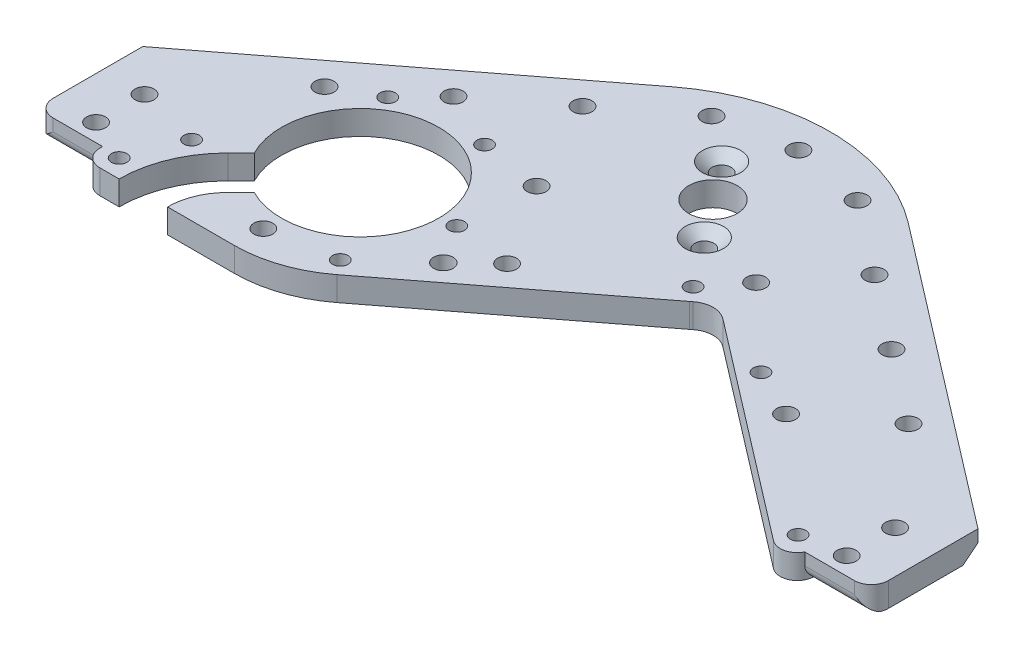
SolidWorks part; units mm, degrees
material "Alum Plate"
ref_plane "Front Plane" through (0, 0, 0) normal (0, 0, 1) x (1, 0, 0)
ref_plane "Top Plane" through (0, 0, 0) normal (0, 1, 0) x (1, 0, 0)
ref_plane "Right Plane" through (0, 0, 0) normal (1, 0, 0) x (0, 0, -1)
sketch "Top Layout" plane through (0, 0, 0) normal (0, 1, 0) x (1, 0, 0)
  line L0 (-114.046, -123.825) -> (-104.775, -123.825) construction
  line L1 (-104.775, -142.875) -> (-101.6, -142.875)
  line L2 (-104.775, -142.875) -> (-104.775, -104.775)
  line L3 (-104.775, -104.775) -> (-101.6, -104.775)
  line L4 (-101.6, -142.875) -> (-101.6, -104.775)
  line L5 (-104.775, -142.875) -> (-101.6, -104.775) construction
  line L6 (-104.775, -104.775) -> (-101.6, -142.875) construction
  line L7 (-19.05, -105.8164) -> (-101.6, -105.8164)
  line L8 (-19.05, -105.8164) -> (-19.05, -141.8336)
  line L9 (-19.05, -141.8336) -> (-101.6, -141.8336)
  line L10 (-101.6, -105.8164) -> (-101.6, -141.8336)
  line L11 (-19.05, -105.8164) -> (-101.6, -141.8336) construction
  line L12 (-19.05, -141.8336) -> (-101.6, -105.8164) construction
  line L13 (-133.096, -85.725) -> (-114.046, -85.725)
  line L14 (-133.096, -85.725) -> (-133.096, -161.925)
  line L15 (-133.096, -161.925) -> (-114.046, -161.925)
  line L16 (-114.046, -85.725) -> (-114.046, -161.925)
  line L17 (-133.096, -85.725) -> (-114.046, -161.925) construction
  line L18 (-133.096, -161.925) -> (-114.046, -85.725) construction
  line L19 (-104.775, -123.825) -> (0, -123.825) construction
  line L20 (0, -123.825) -> (0, 0) construction
  line L21 (-52.3528, -40.1717) -> (0, 0) construction
  line L22 (-70.6449, -16.3328) -> (-18.2922, 23.8388)
  line L23 (-34.0606, -64.0105) -> (18.2922, -23.8388)
  line L24 (-30.9251, 40.3023) -> (-122.2248, -29.7544)
  line L25 (-153.9748, -53.975) -> (-153.9748, -123.825)
  line L26 (-109.5248, -162.052) -> (109.5248, -162.052)
  line L27 (0, -162.052) -> (0, -123.825) construction
  line L28 (-109.5248, -162.052) -> (-109.5248, -20.0093) construction
  line L29 (-104.775, -142.875) -> (-104.775, -152.527)
  line L30 (-104.775, -152.527) -> (104.775, -152.527)
  line L31 (104.775, -104.775) -> (101.6, -104.775)
  line L32 (-144.4498, -73.025) -> (-109.5248, -73.025)
  line L33 (-144.4498, -73.025) -> (-144.4498, -123.825)
  line L34 (-144.4498, -123.825) -> (-109.5248, -123.825) construction
  line L35 (-109.5248, -73.025) -> (-109.5248, -162.052)
  line L36 (-144.4498, -73.025) -> (-109.5248, -123.825) construction
  line L37 (-144.4498, -123.825) -> (-109.5248, -73.025) construction
  line L38 (101.6, -142.875) -> (101.6, -104.775)
  line L39 (104.775, -142.875) -> (101.6, -142.875)
  line L40 (104.775, -142.875) -> (104.775, -104.775)
  line L41 (104.775, -142.875) -> (104.775, -152.527)
  line L42 (109.5248, -162.052) -> (109.5248, -20.0093) construction
  line L43 (30.9251, 40.3023) -> (122.2248, -29.7544)
  line L45 (19.05, -141.8336) -> (101.6, -141.8336)
  line L46 (101.6, -105.8164) -> (101.6, -141.8336)
  line L47 (19.05, -105.8164) -> (101.6, -105.8164)
  line L48 (19.05, -105.8164) -> (19.05, -141.8336)
  line L49 (133.096, -161.925) -> (114.046, -161.925)
  line L50 (114.046, -85.725) -> (114.046, -161.925)
  line L51 (133.096, -85.725) -> (114.046, -85.725)
  line L52 (133.096, -85.725) -> (133.096, -161.925)
  line L53 (144.4498, -123.825) -> (109.5248, -123.825) construction
  line L54 (109.5248, -73.025) -> (109.5248, -162.052)
  line L55 (144.4498, -73.025) -> (109.5248, -73.025)
  line L56 (144.4498, -73.025) -> (144.4498, -123.825)
  line L57 (-109.5248, -123.825) -> (-109.5248, -162.052) construction
  line L62 (-153.9748, -53.975) -> (-122.2248, -53.975)
  line L63 (-122.2248, -53.975) -> (-122.2248, -29.7544)
  line L64 (-144.4498, -123.825) -> (-153.9748, -123.825)
  line L65 (153.9748, -53.975) -> (153.9748, -123.825)
  line L66 (109.5248, -123.825) -> (109.5248, -162.052) construction
  line L67 (144.4498, -123.825) -> (153.9748, -123.825)
  line L68 (122.2248, -29.7544) -> (122.2248, -53.975)
  line L73 (-104.775, -104.775) -> (-104.775, -16.3647) construction
  line L74 (-95.25, -162.052) -> (-95.25, -9.0559) construction
  line L75 (-109.5248, -162.052) -> (-109.5248, -123.825) construction
  line L76 (109.5248, -162.052) -> (109.5248, -123.825) construction
  line L77 (122.2248, -53.975) -> (153.9748, -53.975)
  line L83 (104.775, -155.5496) -> (-104.775, -155.5496) construction
  line L88 (95.25, -162.052) -> (95.25, -9.0559) construction
  line L89 (104.775, -104.775) -> (104.775, -16.3647) construction
  line L92 (-104.775, -152.527) -> (-104.775, -162.052) construction
  line L93 (-14.605, -76.327) -> (14.605, -76.327)
  line L94 (-14.605, -76.327) -> (-14.605, -152.527)
  line L95 (-14.605, -152.527) -> (14.605, -152.527)
  line L96 (14.605, -76.327) -> (14.605, -152.527)
  line L97 (-14.605, -76.327) -> (14.605, -152.527) construction
  line L98 (-14.605, -152.527) -> (14.605, -76.327) construction
  line L99 (104.775, -152.527) -> (104.775, -162.052) construction
  line L100 (-19.05, -105.8164) -> (0, -105.8164) construction
  line L107 (0, -105.8164) -> (19.05, -105.8164) construction
  line L108 (104.775, -123.825) -> (114.046, -123.825) construction
  circle A0 centre (0, 0) radius 114.3
  circle A1 centre (0, 0) radius 6.35
  circle A2 centre (-52.3528, -40.1717) radius 17.8
  circle A3 centre (0, 0) radius 30.0482
  circle A4 centre (-52.3528, -40.1717) radius 30.0482
  arc A5 (-30.9251, 40.3023) -> (30.9251, 40.3023) centre (0, 0) cw
  point P2 (-103.1875, -123.825)
  point P7 (-60.325, -123.825)
  point P12 (-123.571, -123.825)
  point P30 (-126.9873, -98.425)
  point P35 (0, -114.427)
  point P53 (0, -152.527)
  dimension "D1" = 35.6
  dimension "D2" = 12.7
  dimension "D3" = 228.6
  dimension "D11" = 60.0964
  dimension "D12" = 50.8
  dimension "D14" = 52.5
  dimension "D4" = 3.175
  dimension "D5" = 19.05
  dimension "D6" = 76.2
  dimension "D7" = 82.55
  dimension "D8" = 38.1
  dimension "D9" = 104.775
  dimension "D10" = 18.0086
  dimension "D13" = 9.525
  dimension "D15" = 4.7498
  dimension "D16" = 9.525
  dimension "D17" = 9.652
  dimension "D18" = 50.8
  dimension "D19" = 12.446
  dimension "D20" = 65.9892
  dimension "D21" = 19.05
  dimension "D22" = 34.925
  dimension "D23" = 123.825
  dimension "D24" = 12.7
  dimension "D25" = 9.525
  dimension "D26" = 29.21
  dimension "D27" = 76.2
  dimension "D28" = 3.0226
sketch "Side Layout" plane through (0, 0, 0) normal (1, 0, 0) x (0, 0, -1)
  line L0 (0, -38.1) -> (0, 33.7344) construction
  line L1 (-114.3, -20.955) -> (114.3, -20.955)
  line L2 (-114.3, -20.955) -> (-114.3, -33.655)
  line L3 (-114.3, -33.655) -> (114.3, -33.655)
  line L4 (114.3, -20.955) -> (114.3, -33.655)
  line L5 (-114.3, -20.955) -> (114.3, -33.655) construction
  line L6 (-114.3, -33.655) -> (114.3, -20.955) construction
  line L7 (-9.525, -32.9406) -> (9.525, -32.9406)
  line L8 (-9.525, -32.9406) -> (-9.525, -38.1)
  line L9 (-9.525, -38.1) -> (9.525, -38.1)
  line L10 (9.525, -32.9406) -> (9.525, -38.1)
  line L11 (-9.525, -32.9406) -> (9.525, -38.1) construction
  line L12 (-9.525, -38.1) -> (9.525, -32.9406) construction
  line L13 (-11.9126, -29.3338) -> (11.9126, -29.3338)
  line L14 (-11.9126, -29.3338) -> (-11.9126, -32.9406)
  line L15 (-11.9126, -32.9406) -> (11.9126, -32.9406)
  line L16 (11.9126, -29.3338) -> (11.9126, -32.9406)
  line L17 (-11.9126, -29.3338) -> (11.9126, -32.9406) construction
  line L18 (-11.9126, -32.9406) -> (11.9126, -29.3338) construction
  line L19 (-6.35, -32.9406) -> (6.35, -32.9406)
  line L20 (-6.35, -32.9406) -> (-6.35, 33.7344)
  line L21 (-6.35, 33.7344) -> (6.35, 33.7344)
  line L22 (6.35, -32.9406) -> (6.35, 33.7344)
  line L23 (-6.35, -32.9406) -> (6.35, 33.7344) construction
  line L24 (-6.35, 33.7344) -> (6.35, -32.9406) construction
  line L25 (-162.052, 0) -> (-123.825, 0) construction
  line L26 (114.3, -33.655) -> (114.3, 0) construction
  line L27 (-142.875, 19.05) -> (-104.775, 19.05)
  line L28 (-40.1717, -9.525) -> (-40.1717, 5.4) construction
  line L29 (-142.875, 19.05) -> (-142.875, -19.05)
  line L30 (-142.875, -19.05) -> (-104.775, -19.05)
  line L31 (-104.775, 19.05) -> (-104.775, -19.05)
  line L32 (-142.875, 19.05) -> (-104.775, -19.05) construction
  line L33 (-142.875, -19.05) -> (-104.775, 19.05) construction
  line L34 (-130.175, -38.1) -> (-117.9516, -38.1) construction
  line L35 (-57.9717, -14.6) -> (-22.3717, -14.6)
  line L36 (-30.0482, -2.794) -> (30.0482, -2.794)
  line L37 (-30.0482, -2.794) -> (-30.0482, -20.955)
  line L38 (-30.0482, -20.955) -> (30.0482, -20.955)
  line L39 (30.0482, -2.794) -> (30.0482, -20.955)
  line L40 (-30.0482, -2.794) -> (30.0482, -20.955) construction
  line L41 (-30.0482, -20.955) -> (30.0482, -2.794) construction
  line L42 (-30.0482, -2.794) -> (-30.0482, 0) construction
  line L43 (-123.825, 0) -> (0, 0) construction
  line L44 (-57.9717, -14.6) -> (-57.9717, 25.4)
  line L45 (-57.9717, 25.4) -> (-22.3717, 25.4)
  line L46 (-22.3717, -14.6) -> (-22.3717, 25.4)
  line L47 (-19.05, 0) -> (19.05, 0)
  line L48 (-19.05, 0) -> (-19.05, -1.9812)
  line L49 (-19.05, -1.9812) -> (19.05, -1.9812)
  line L50 (19.05, 0) -> (19.05, -1.9812)
  line L51 (-19.05, 0) -> (19.05, -1.9812) construction
  line L52 (-19.05, -1.9812) -> (19.05, 0) construction
  line L53 (-70.2199, -3.175) -> (-10.1235, -3.175)
  line L54 (-70.2199, -3.175) -> (-70.2199, -15.875)
  line L55 (-70.2199, -15.875) -> (-10.1235, -15.875)
  line L56 (-10.1235, -3.175) -> (-10.1235, -15.875)
  line L57 (-70.2199, -3.175) -> (-10.1235, -15.875) construction
  line L58 (-70.2199, -15.875) -> (-10.1235, -3.175) construction
  line L59 (-40.1717, -9.525) -> (-40.1717, 0) construction
  line L60 (-57.9717, -14.6) -> (-22.3717, 25.4) construction
  line L61 (-57.9717, 25.4) -> (-22.3717, -14.6) construction
  line L62 (-22.3717, 0) -> (-57.9717, 0) construction
  line L63 (-137.8162, 0) -> (-123.825, -13.9912) construction
  line L64 (-139.065, 15.24) -> (-108.585, 15.24) construction
  line L65 (-139.065, 15.24) -> (-139.065, -15.24) construction
  line L66 (-139.065, -15.24) -> (-108.585, -15.24) construction
  line L67 (-108.585, 15.24) -> (-108.585, -15.24) construction
  line L68 (-139.065, 15.24) -> (-108.585, -15.24) construction
  line L69 (-139.065, -15.24) -> (-108.585, 15.24) construction
  line L70 (-137.8162, 0) -> (-123.825, 13.9912) construction
  line L71 (-123.825, -13.9912) -> (-109.8338, 0) construction
  line L72 (-123.825, 13.9912) -> (-109.8338, 0) construction
  line L73 (-137.8162, 0) -> (-109.8338, 0) construction
  line L74 (-123.825, -13.9912) -> (-123.825, 13.9912) construction
  line L75 (-6.35, 17.8594) -> (6.35, 17.8594)
  line L76 (114.3, 0) -> (-114.3, 0) construction
  line L77 (-22.3717, 19.05) -> (-6.35, 19.05) construction
  line L78 (-123.825, 38.1) -> (-97.9206, 38.1) construction
  line L79 (-19.05, -3.5814) -> (19.05, -3.5814)
  line L80 (-19.05, -3.5814) -> (-19.05, -1.9812)
  line L81 (-19.05, -1.9812) -> (19.05, -1.9812)
  line L82 (19.05, -3.5814) -> (19.05, -1.9812)
  line L83 (-19.05, -3.5814) -> (19.05, -1.9812) construction
  line L84 (-19.05, -1.9812) -> (19.05, -3.5814) construction
  line L85 (-8.7376, -16.7608) -> (8.7376, -16.7608)
  line L86 (-8.7376, -16.7608) -> (-8.7376, -29.3338)
  line L87 (-8.7376, -29.3338) -> (8.7376, -29.3338)
  line L88 (8.7376, -16.7608) -> (8.7376, -29.3338)
  line L89 (-8.7376, -16.7608) -> (8.7376, -29.3338) construction
  line L90 (-8.7376, -29.3338) -> (8.7376, -16.7608) construction
  line L91 (-8.7376, -3.5814) -> (8.7376, -3.5814)
  line L92 (-8.7376, -3.5814) -> (-8.7376, -16.1544)
  line L93 (-8.7376, -16.1544) -> (8.7376, -16.1544)
  line L94 (8.7376, -3.5814) -> (8.7376, -16.1544)
  line L95 (-8.7376, -3.5814) -> (8.7376, -16.1544) construction
  line L96 (-8.7376, -16.1544) -> (8.7376, -3.5814) construction
  circle A0 centre (-123.825, 0) radius 18.0086
  circle A1 centre (-123.825, 0) radius 38.1
  circle A2 centre (-139.065, 15.24) radius 1.905
  circle A3 centre (-108.585, 15.24) radius 1.905
  circle A4 centre (-108.585, -15.24) radius 1.905
  circle A5 centre (-139.065, -15.24) radius 1.905
  circle A6 centre (-137.8162, 0) radius 1.6002
  circle A7 centre (-123.825, 13.9912) radius 1.6002
  circle A8 centre (-109.8338, 0) radius 1.6002
  circle A9 centre (-123.825, -13.9912) radius 1.6002
  point P0 (0, -27.305)
  point P6 (0, -31.1372)
  point P7 (0, -35.5203)
  point P21 (0, 0.3969)
  point P32 (0, -11.8745)
  point P43 (0, -0.9906)
  point P55 (-40.1717, -9.525)
  point P72 (-40.1717, 5.4)
  point P88 (0, -23.0473)
  point P93 (0, -2.7813)
  point P102 (0, -9.8679)
  dimension "D17" = 3.81
  dimension "D18" = 3.2004
  dimension "D1" = 12.7
  dimension "D2" = 5.1594
  dimension "D3" = 19.05
  dimension "D4" = 3.6068
  dimension "D5" = 23.8252
  dimension "D6" = 12.7
  dimension "D7" = 18.161
  dimension "D8" = 1.9812
  dimension "D9" = 12.7
  dimension "D10" = 40
  dimension "D11" = 25.4
  dimension "D12" = 50.8
  dimension "D13" = 41.275
  dimension "D14" = 30.48
  dimension "D15" = 4.445
  dimension "D16" = 19.7866
  dimension "D19" = 15.875
  dimension "D20" = 6.35
  dimension "D21" = 38.1
  dimension "D22" = 1.6002
  dimension "D23" = 38.1
  dimension "D24" = 17.4752
  dimension "D25" = 12.573
ref_plane "Plane1" through (0, 25.4, 0) normal (0, 1, 0) x (1, 0, 0)
sketch "Sketch3" plane through (0, 25.4, 0) normal (0, 1, 0) x (1, 0, 0)
  line L0 (-104.775, -36.3747) -> (-30.9251, 20.2924)
  line L1 (-104.775, -104.775) -> (-104.775, -16.3647) construction
  line L2 (0, -200130.175) -> (0, 199882.0484) construction
  line L3 (-30.9251, 40.3023) -> (-122.2248, -29.7544) construction
  line L5 (-104.775, -36.3747) -> (-104.775, -77.6497)
  line L6 (-92.075, -77.6497) -> (-104.775, -77.6497)
  line L7 (30.9251, 20.2924) -> (104.775, -36.3747)
  line L8 (104.775, -77.6497) -> (92.075, -77.6497)
  line L9 (104.775, -36.3747) -> (104.775, -77.6497)
  line L11 (104.775, -104.775) -> (104.775, -16.3647) construction
  line L12 (30.9251, 40.3023) -> (122.2248, -29.7544) construction
  line L13 (92.075, -74.6536) -> (24.1423, -22.5271)
  line L14 (-32.2514, -66.3682) -> (20.1013, -26.1965)
  line L15 (-30.9251, 20.2924) -> (0, 44.022)
  line L16 (0, 44.022) -> (30.9251, 20.2924)
  line L17 (-92.075, -77.6497) -> (-92.075, -73.1917)
  line L19 (-92.075, -73.1917) -> (-52.3528, -73.1917)
  line L20 (92.075, -74.6536) -> (92.075, -77.6497)
  circle A1 centre (-52.3528, -40.1717) radius 20.6375
  circle A2 centre (0, 0) radius 6.35
  circle A3 centre (0, 0) radius 6.35 construction
  arc A4 (-52.3528, -73.1917) -> (-32.2514, -66.3682) centre (-52.3528, -40.1717) ccw
  arc A5 (20.1013, -26.1965) -> (24.1423, -22.5271) centre (0, 0) ccw
  arc A6 (30.9251, 20.2924) -> (-30.9251, 20.2924) centre (0, -20.01) ccw construction
  point P28 (0, 44.022)
  dimension "D1" = 33.02
  dimension "D5" = 50.8
  dimension "D7" = 41.275
  dimension "D2" = 41.275
  dimension "D3" = 34.925
  dimension "D4" = 12.7
  dimension "D6" = 38.1
extrude "Boss-Extrude1" add sketch "Sketch3" against normal blind 6.35
ref_plane "Plane3" through (-104.775, 0, 0) normal (-1, 0, 0) x (0, 0, 1)
sketch "Sketch6" plane through (-104.775, 0, 0) normal (-1, 0, 0) x (0, 0, 1)
  line L0 (162.052, -25.4) -> (162.052, 25.4)
  line L1 (162.052, 25.4) -> (77.6497, 25.4)
  line L2 (36.3747, 25.4) -> (77.6497, 25.4) construction
  line L3 (147.7645, 11.1125) -> (162.052, 11.1125) construction
  line L4 (162.052, 0) -> (71.2997, 0) construction
  line L5 (77.6497, 25.4) -> (77.6497, 19.05)
  line L6 (77.6497, 19.05) -> (36.3747, 19.05)
  line L7 (36.3747, 19.05) -> (36.3747, 6.35)
  line L8 (36.3747, 6.35) -> (71.2997, 6.35)
  line L10 (99.6315, -3.175) -> (99.6315, 11.1125) construction
  line L11 (71.2997, -25.4) -> (162.052, -25.4)
  line L13 (71.2997, 6.35) -> (71.2997, -25.4)
  line L14 (152.527, -25.4) -> (152.527, 25.4) construction
  line L15 (99.6315, 11.1125) -> (99.6315, 25.4) construction
  line L16 (147.7645, 11.1125) -> (147.7645, 25.4) construction
  line L17 (94.869, -7.9375) -> (104.394, -7.9375) construction
  line L18 (94.869, -7.9375) -> (94.869, 25.4) construction
  line L19 (94.869, 25.4) -> (104.394, 25.4) construction
  line L20 (104.394, -7.9375) -> (104.394, 25.4) construction
  line L21 (94.869, -7.9375) -> (104.394, 25.4) construction
  line L22 (94.869, 25.4) -> (104.394, -7.9375) construction
  line L23 (147.7645, 11.1125) -> (147.7645, -3.175) construction
  line L24 (104.394, -7.9375) -> (123.825, -7.9375) construction
  line L25 (143.002, -7.9375) -> (152.527, -7.9375) construction
  line L26 (143.002, -7.9375) -> (143.002, 25.4) construction
  line L27 (143.002, 25.4) -> (152.527, 25.4) construction
  line L28 (152.527, -7.9375) -> (152.527, 25.4) construction
  line L29 (143.002, -7.9375) -> (152.527, 25.4) construction
  line L30 (143.002, 25.4) -> (152.527, -7.9375) construction
  line L31 (123.825, -7.9375) -> (152.527, -7.9375) construction
  line L32 (104.775, 19.05) -> (104.775, -19.05) construction
  line L34 (155.702, -25.4) -> (155.702, 25.4) construction
  circle A0 centre (109.8338, 0) radius 1.6002 construction
  circle A1 centre (123.825, 13.9912) radius 1.6002 construction
  circle A2 centre (137.8162, 0) radius 1.6002 construction
  circle A3 centre (123.825, -13.9912) radius 1.6002 construction
  circle A4 centre (109.8338, 0) radius 1.6002 construction
  circle A5 centre (123.825, 13.9912) radius 1.6002 construction
  circle A6 centre (137.8162, 0) radius 1.6002 construction
  circle A7 centre (123.825, -13.9912) radius 1.6002 construction
  circle A8 centre (123.825, 0) radius 18.0086 construction
  circle A9 centre (123.825, 0) radius 18.0086 construction
  circle A10 centre (123.825, 0) radius 9.525
  circle A11 centre (108.585, -15.24) radius 1.905 construction
  circle A12 centre (108.585, 15.24) radius 1.905 construction
  circle A13 centre (139.065, 15.24) radius 1.905 construction
  circle A14 centre (139.065, -15.24) radius 1.905 construction
  circle A15 centre (108.585, -15.24) radius 1.905
  circle A16 centre (108.585, 15.24) radius 1.905
  circle A17 centre (139.065, 15.24) radius 1.905
  circle A18 centre (139.065, -15.24) radius 1.905
  circle A19 centre (147.7645, 11.1125) radius 2.5527
  circle A26 centre (99.6315, 11.1125) radius 2.5527
  circle A27 centre (99.6315, -3.175) radius 2.5527
  circle A28 centre (147.7645, -3.175) radius 2.5527
  point P29 (0, 0)
  point P55 (99.6315, 8.7312)
  point P61 (147.7645, 8.7312)
  dimension "D4" = 19.05
  dimension "D7" = 5.1054
  dimension "D1" = 6.35
  dimension "D2" = 12.7
  dimension "D3" = 25.4
  dimension "D5" = 6.35
  dimension "D6" = 3.175
  dimension "D8" = 0.381
  dimension "D9" = 14.2875
  dimension "D10" = 9.525
  dimension "D12" = 33.3375
sketch "Sketch12" [suppressed] plane through (0, 19.05, 0) normal (0, 1, 0) x (1, 0, 0)
  line L0 (-104.775, -77.6497) -> (-104.775, -36.3747)
  line L1 (-104.775, -36.3747) -> (-92.075, -36.3747)
  line L3 (-92.075, -36.3747) -> (-92.075, -77.6497)
  line L5 (-92.075, -77.6497) -> (-104.775, -77.6497)
  line L6 (-98.425, -77.6497) -> (-98.425, -63.3622) construction
  line L7 (-98.425, -63.3622) -> (-98.425, -50.6622) construction
  line L8 (-98.425, -50.6622) -> (-98.425, -36.3747) construction
  line L10 (-98.425, -36.3747) -> (-104.775, -36.3747) construction
  circle A0 centre (-98.425, -63.3622) radius 2.5527
  circle A1 centre (-98.425, -50.6622) radius 2.5527
  dimension "D2" = 5.1054
  dimension "D1" = 12.7
  dimension "D3" = 12.7
sketch "Sketch8" plane through (0, 25.4, 0) normal (0, 1, 0) x (1, 0, 0)
  line L0 (-109.5248, -162.052) -> (-109.5248, -20.0093) construction
  line L1 (-104.775, -77.6497) -> (-109.5248, -77.6497)
  line L2 (-104.775, -77.6497) -> (-104.775, -36.3747)
  line L3 (-104.775, -36.3747) -> (-109.5248, -36.3747)
  line L4 (-109.5248, -77.6497) -> (-109.5248, -36.3747)
  line L5 (-104.775, -77.6497) -> (-109.5248, -36.3747) construction
  line L6 (-104.775, -36.3747) -> (-109.5248, -77.6497) construction
  line L7 (104.775, -77.6497) -> (109.5248, -77.6497)
  line L8 (104.775, -77.6497) -> (104.775, -36.3747)
  line L9 (104.775, -36.3747) -> (109.5248, -36.3747)
  line L10 (109.5248, -77.6497) -> (109.5248, -36.3747)
  line L11 (104.775, -77.6497) -> (109.5248, -36.3747) construction
  line L12 (104.775, -36.3747) -> (109.5248, -77.6497) construction
  point P4 (-107.1499, -57.0122)
  point P10 (107.1499, -57.0122)
extrude "Boss-Extrude4" add sketch "Sketch8" against normal through all
sketch "Sketch9" plane through (0, 25.4, 0) normal (0, 1, 0) x (1, 0, 0)
  line L0 (7.4916, -9.7632) -> (0, 0) construction
  line L1 (0, 0) -> (-7.4916, 9.7632) construction
  line L2 (0, 44.022) -> (-104.775, -36.3747) construction
  circle A0 centre (-7.4916, 9.7632) radius 2.4892
  circle A1 centre (7.4916, -9.7632) radius 2.4892
  dimension "D2" = 4.9784
  dimension "D1" = 24.6126
extrude "Collar Holes" cut sketch "Sketch9" against normal through all
sketch "Sketch10" plane through (0, 25.4, 0) normal (0, 1, 0) x (1, 0, 0)
  line L0 (0, 33.4567) -> (0, 30.79) construction
  line L1 (-5.1026, 40.1066) -> (0, 33.4567) construction
  line L2 (0, 33.4567) -> (5.1026, 40.1066) construction
  line L3 (0, 44.022) -> (-104.775, -36.3747) construction
  line L4 (104.775, -36.3747) -> (0, 44.022) construction
  circle A0 centre (0, 33.4567) radius 4.7625 construction
  circle A1 centre (0, 33.4567) radius 2.0193
  arc A3 (30.9251, 20.2924) -> (-30.9251, 20.2924) centre (0, -20.01) ccw construction
  dimension "D2" = 9.525
  dimension "D3" = 4.0386
  dimension "D1" = 8.382
extrude "Spacer Holes" cut sketch "Sketch10" against normal through all
pattern_linear "Spacer Hole Pattern" count 5 spacing 24.13 along (-0.7934, 0, 0.6088) of "Spacer Holes"
mirror "Spacer Hole Mirror" about plane through (0, 0, 0) normal (1, 0, 0) of "Spacer Hole Pattern"
sketch "Sketch16" plane through (0, 25.4, 0) normal (0, 1, 0) x (1, 0, 0)
  line L0 (-109.5248, -50.6622) -> (-98.425, -50.6622) construction
  line L1 (-109.5248, -36.3747) -> (-109.5248, -77.6497) construction
  line L2 (-98.425, -50.6622) -> (-98.425, -63.3622) construction
  line L3 (-98.425, -63.3622) -> (-109.5248, -63.3622) construction
  line L4 (-98.425, -63.3622) -> (-98.425, -77.6497) construction
  line L5 (-109.5248, -77.6497) -> (-92.075, -77.6497) construction
  line L6 (-98.425, -50.6622) -> (-98.425, -36.3747) construction
  line L7 (-104.775, -36.3747) -> (-109.5248, -36.3747) construction
  line L8 (-104.775, -36.3747) -> (-104.775, -77.6497) construction
  line L9 (0, 0) -> (0, 30.79) construction
  line L10 (104.775, -36.3747) -> (104.775, -77.6497) construction
  circle A0 centre (-98.425, -50.6622) radius 2.0193
  circle A1 centre (-98.425, -63.3622) radius 2.0193
  circle A4 centre (98.425, -63.3622) radius 2.0193
  circle A5 centre (98.425, -50.6622) radius 2.0193
  arc A6 (30.9251, 20.2924) -> (-30.9251, 20.2924) centre (0, -20.01) ccw construction
  dimension "D1" = 4.0386
  dimension "D2" = 12.7
  dimension "D3" = 6.35
extrude "Custom Nutstrip Holes" cut sketch "Sketch16" against normal through all
sketch "Sketch36" plane through (0, 25.4, 0) normal (0, 1, 0) x (1, 0, 0)
  line L0 (-52.3528, -65.5717) -> (-12.44, -41.5615) construction
  line L1 (-12.44, -41.5615) -> (24.5129, -13.2066) construction
  line L2 (24.5129, -13.2066) -> (58.2939, -39.1277) construction
  line L3 (-32.2514, -66.3682) -> (20.1013, -26.1965) construction
  line L4 (24.1423, -22.5271) -> (92.075, -74.6536) construction
  line L5 (-12.44, -41.5615) -> (-7.8012, -47.6069) construction
  line L6 (58.2939, -39.1277) -> (53.6552, -45.1731) construction
  line L7 (-52.3528, -65.5717) -> (-52.3528, -40.1717) construction
  line L8 (58.2939, -39.1277) -> (92.075, -65.0488) construction
  line L9 (92.075, -65.0488) -> (92.075, -77.6497) construction
  line L10 (-52.3528, -40.1717) -> (-26.1764, -20.0858) construction
  line L11 (-26.1764, -20.0858) -> (0, 0) construction
  line L12 (92.075, -74.6536) -> (92.075, -77.6497) construction
  circle A0 centre (-52.3528, -65.5717) radius 2.0193
  circle A1 centre (58.2939, -39.1277) radius 2.0193
  circle A2 centre (24.5129, -13.2066) radius 2.0193
  circle A3 centre (-12.44, -41.5615) radius 2.0193
  circle A4 centre (-76.5745, -25.3009) radius 2.0193 construction
  circle A5 centre (-52.3528, -65.5717) radius 4.7625 construction
  circle A6 centre (-12.44, -41.5615) radius 4.7625 construction
  circle A7 centre (24.5129, -13.2066) radius 4.7625 construction
  circle A8 centre (58.2939, -39.1277) radius 4.7625 construction
  arc A9 (-52.3528, -73.1917) -> (-32.2514, -66.3682) centre (-52.3528, -40.1717) ccw construction
  circle A10 centre (-26.1764, -20.0858) radius 2.0193
  dimension "D1" = 9.525
  dimension "D2" = 25.4
  dimension "D3" = 7.62
extrude "Aux Spacer Holes" cut sketch "Sketch36" against normal through all
sketch "Sketch38" [suppressed] plane through (-104.775, 0, 0) normal (-1, 0, 0) x (0, 0, 1)
  line L1 (152.527, -7.9375) -> (143.002, -7.9375)
  line L2 (152.527, -7.9375) -> (152.527, 25.4)
  line L3 (152.527, 25.4) -> (143.002, 25.4)
  line L4 (143.002, -7.9375) -> (143.002, 25.4)
  line L5 (152.527, -7.9375) -> (143.002, 25.4) construction
  line L6 (152.527, 25.4) -> (143.002, -7.9375) construction
  point P4 (147.7645, 8.7312)
extrude "Cut-Extrude16" [suppressed] cut sketch "Sketch38" against normal blind 9.525
sketch "Sketch46" [suppressed] plane through (-104.775, 0, 0) normal (-1, 0, 0) x (0, 0, 1)
  line L0 (142.875, 19.05) -> (104.775, -19.05) construction
  line L1 (104.14, 19.685) -> (143.51, 19.685)
  line L2 (104.14, 19.685) -> (104.14, -19.685)
  line L3 (104.14, -19.685) -> (143.51, -19.685)
  line L4 (143.51, 19.685) -> (143.51, -19.685)
  line L5 (104.14, 19.685) -> (143.51, -19.685) construction
  line L6 (104.14, -19.685) -> (143.51, 19.685) construction
  point P0 (123.825, 0)
  dimension "D1" = 39.37
extrude "Cut-Extrude21" [suppressed] cut sketch "Sketch46" against normal blind 6.985
ref_plane "Plane5" through (0, 0, 152.527) normal (0, 0, 1) x (1, 0, 0)
sketch "Sketch41" plane through (0, 0, 152.527) normal (0, 0, 1) x (1, 0, 0)
  line L0 (-104.775, -7.9375) -> (-104.775, 25.4) construction
  line L1 (-104.775, -7.9375) -> (-104.775, 12.7)
  line L2 (-104.775, -7.9375) -> (104.775, -7.9375)
  line L3 (104.775, -7.9375) -> (104.775, 12.7)
  line L4 (104.775, 25.4) -> (-104.775, 25.4)
  line L5 (0, -7.9375) -> (0, 25.4) construction
  line L6 (-104.775, 3.9624) -> (-100.0125, 3.9624) construction
  line L7 (-100.0125, 3.9624) -> (-100.0125, 25.4) construction
  line L8 (104.775, 3.9624) -> (100.0125, 3.9624) construction
  line L9 (100.0125, 3.9624) -> (100.0125, 25.4) construction
  line L10 (19.05, 20.6375) -> (23.8252, 20.6375) construction
  line L11 (19.05, 15.875) -> (78.5876, 15.875) construction
  line L12 (19.05, 15.875) -> (19.05, 25.4) construction
  line L13 (19.05, 25.4) -> (78.5876, 25.4) construction
  line L14 (78.5876, 15.875) -> (78.5876, 25.4) construction
  line L15 (19.05, 15.875) -> (78.5876, 25.4) construction
  line L16 (19.05, 25.4) -> (78.5876, 15.875) construction
  line L17 (23.8252, 20.6375) -> (38.1127, 20.6375) construction
  line L18 (38.1127, 20.6375) -> (52.4002, 20.6375) construction
  line L19 (52.4002, 20.6375) -> (66.6877, 20.6375) construction
  line L20 (-104.775, 25.4) -> (-112.395, 25.4)
  line L21 (-112.395, 25.4) -> (-112.395, 3.175)
  line L22 (-112.395, 3.175) -> (-109.5248, 3.175)
  line L23 (-109.5248, 3.175) -> (-109.5248, 12.7)
  line L24 (-109.5248, 12.7) -> (-104.775, 12.7)
  line L25 (-104.775, 12.7) -> (-104.775, 25.4) construction
  line L26 (104.775, 25.4) -> (112.395, 25.4)
  line L27 (112.395, 25.4) -> (112.395, 3.175)
  line L28 (112.395, 3.175) -> (109.5248, 3.175)
  line L29 (109.5248, 3.175) -> (109.5248, 12.7)
  line L30 (109.5248, 12.7) -> (104.775, 12.7)
  line L31 (104.775, 12.7) -> (104.775, 25.4) construction
  line L32 (-100.0125, 3.9624) -> (-87.3125, 3.9624) construction
  line L33 (-63.5, -1.5875) -> (0, -1.5875) construction
  line L34 (0, -1.5875) -> (63.5, -1.5875) construction
  line L35 (63.5, -1.5875) -> (63.5, -7.9375) construction
  circle A0 centre (-100.0125, 3.9624) radius 2.5527
  circle A1 centre (100.0125, 3.9624) radius 2.5527
  circle A2 centre (23.8252, 20.6375) radius 2.5527
  circle A3 centre (38.1127, 20.6375) radius 2.5527
  circle A4 centre (52.4002, 20.6375) radius 2.5527
  circle A5 centre (66.6877, 20.6375) radius 2.5527
  circle A6 centre (-66.6877, 20.6375) radius 2.5527
  circle A7 centre (-52.4002, 20.6375) radius 2.5527
  circle A8 centre (-38.1127, 20.6375) radius 2.5527
  circle A9 centre (-23.8252, 20.6375) radius 2.5527
  circle A10 centre (-87.3125, 3.9624) radius 2.5527
  circle A11 centre (87.3125, 3.9624) radius 2.5527
  circle A12 centre (-63.5, -1.5875) radius 2.5527
  circle A13 centre (63.5, -1.5875) radius 2.5527
  point P14 (48.8188, 20.6375)
  dimension "D3" = 5.1054
  dimension "D7" = 5.1054
  dimension "D1" = 21.4376
  dimension "D2" = 4.7625
  dimension "D4" = 9.525
  dimension "D5" = 59.5376
  dimension "D6" = 4.7752
  dimension "D8" = 14.2875
  dimension "D9" = 7.62
  dimension "D10" = 4.7498
  dimension "D11" = 12.7
  dimension "D12" = 9.525
  dimension "D13" = 19.05
  dimension "D14" = 12.7
  dimension "D15" = 6.35
  dimension "D16" = 63.5
sketch "Sketch43" [suppressed] plane through (-109.5248, 0, 0) normal (-1, 0, 0) x (0, 0, 1)
  line L1 (152.527, 12.7) -> (155.702, 12.7)
  line L2 (152.527, 12.7) -> (152.527, 25.4)
  line L3 (152.527, 25.4) -> (155.702, 25.4)
  line L4 (155.702, 12.7) -> (155.702, 25.4)
  line L5 (152.527, 12.7) -> (155.702, 25.4) construction
  line L6 (152.527, 25.4) -> (155.702, 12.7) construction
  line L7 (162.052, 25.4) -> (77.6497, 25.4) construction
  point P4 (154.1145, 19.05)
  dimension "D1" = 3.175
sketch "Sketch44" plane through (0, 25.4, 0) normal (0, 1, 0) x (1, 0, 0)
  line L0 (73.8315, -147.7645) -> (73.8315, -152.527) construction
  line L1 (92.075, -74.6536) -> (92.075, -77.6497) construction
  line L2 (-92.075, -77.6497) -> (-92.075, -73.1917) construction
  line L3 (0, -123.825) -> (0, 0) construction
  line L4 (-92.075, -73.1917) -> (-52.3528, -73.1917) construction
  line L5 (-104.775, -104.775) -> (-104.775, -16.3647) construction
  line L6 (-32.2514, -66.3682) -> (20.1013, -26.1965) construction
  line L21 (-104.775, -68.1247) -> (-104.775, -152.527)
  line L22 (-104.775, -152.527) -> (104.775, -152.527)
  line L23 (104.775, -152.527) -> (104.775, -68.1247)
  line L34 (-104.775, -99.6315) -> (-100.0125, -99.6315) construction
  line L35 (-104.775, -147.7645) -> (-100.0125, -147.7645) construction
  line L36 (0, -152.527) -> (0, -35.6178) construction
  line L38 (30.969, -147.7645) -> (45.2565, -147.7645) construction
  line L39 (45.2565, -147.7645) -> (59.544, -147.7645) construction
  line L40 (59.544, -147.7645) -> (73.8315, -147.7645) construction
  line L41 (23.8252, -152.527) -> (30.969, -152.527) construction
  line L42 (104.775, -152.527) -> (-104.775, -152.527) construction
  line L43 (30.969, -152.527) -> (38.1127, -152.527) construction
  line L44 (30.969, -152.527) -> (30.969, -147.7645) construction
  line L45 (-92.075, -77.6497) -> (-104.775, -77.6497) construction
  line L48 (-35.1507, -62.5899) -> (-8.9743, -42.504) construction
  line L49 (-8.9743, -42.504) -> (17.2021, -22.4182) construction
  line L50 (45.5313, -32.9364) -> (87.3125, -64.9962) construction
  line L51 (92.075, -74.6536) -> (24.1423, -22.5271) construction
  line L52 (104.775, -77.6497) -> (92.075, -77.6497) construction
  line L79 (-104.775, -68.1247) -> (-92.075, -68.1247)
  line L80 (-92.075, -68.1247) -> (-92.075, -63.6667)
  line L85 (21.8118, -8.7328) -> (92.075, -62.6476)
  line L86 (-38.0499, -58.8115) -> (14.3028, -18.6398)
  line L87 (-92.075, -63.6667) -> (-52.3528, -63.6667)
  line L88 (92.075, -62.6476) -> (92.075, -68.1247)
  line L89 (92.075, -68.1247) -> (104.775, -68.1247)
  circle A0 centre (-73.8315, -147.7645) radius 2.5527
  circle A1 centre (-59.544, -147.7645) radius 2.5527
  circle A2 centre (-45.2565, -147.7645) radius 2.5527
  circle A3 centre (-30.969, -147.7645) radius 2.5527
  circle A17 centre (-100.0125, -99.6315) radius 2.5527
  circle A18 centre (-100.0125, -147.7645) radius 2.5527
  circle A19 centre (100.0125, -147.7645) radius 2.5527
  circle A20 centre (100.0125, -99.6315) radius 2.5527
  circle A21 centre (30.969, -147.7645) radius 2.5527
  circle A22 centre (45.2565, -147.7645) radius 2.5527
  circle A23 centre (59.544, -147.7645) radius 2.5527
  circle A24 centre (73.8315, -147.7645) radius 2.5527
  circle A25 centre (-87.3125, -68.4292) radius 4.7625 construction
  circle A26 centre (-35.1507, -62.5899) radius 4.7625 construction
  circle A27 centre (-8.9743, -42.504) radius 4.7625 construction
  circle A28 centre (17.2021, -22.4182) radius 4.7625 construction
  circle A29 centre (45.5313, -32.9364) radius 4.7625 construction
  circle A30 centre (87.3125, -64.9962) radius 4.7625 construction
  circle A32 centre (-87.3125, -68.4292) radius 2.5527
  circle A33 centre (-35.1507, -62.5899) radius 2.5527
  circle A34 centre (-8.9743, -42.504) radius 2.5527 construction
  circle A35 centre (17.2021, -22.4182) radius 2.5527
  circle A36 centre (45.5313, -32.9364) radius 2.5527
  circle A37 centre (87.3125, -64.9962) radius 2.5527
  circle A38 centre (-97.155, -85.2697) radius 7.62 construction
  circle A39 centre (97.155, -85.2697) radius 7.62 construction
  circle A40 centre (24.5121, -32.4156) radius 7.62 construction
  arc A41 (20.1013, -26.1965) -> (24.1423, -22.5271) centre (0, 0) ccw construction
  circle A42 centre (-97.155, -85.2697) radius 2.5527
  circle A43 centre (24.5121, -32.4156) radius 2.5527
  circle A44 centre (97.155, -85.2697) radius 2.5527
  arc A56 (14.3028, -18.6398) -> (21.8118, -8.7328) centre (0, 0) ccw
  arc A57 (-52.3528, -63.6667) -> (-38.0499, -58.8115) centre (-52.3528, -40.1717) ccw
  point P4 (-104.775, -152.527)
  dimension "D2" = 5.1054
  dimension "D7" = 5.1054
  dimension "D8" = 15.24
  dimension "D3" = 9.525
  dimension "D9" = 9.525
  dimension "D4" = 4.7625
  dimension "D5" = 14.2875
  dimension "D6" = 9.525
  dimension "D1" = 4.7625
  dimension "D10" = 52.664
sketch "Sketch82" [suppressed] plane through (0, 28.829, 0) normal (0, 1, 0) x (1, 0, 0)
  line L0 (-52.3528, -63.6667) -> (-92.075, -63.6667) construction
  line L1 (-52.3528, -65.5717) -> (-52.3528, -63.6667) construction
  line L2 (-12.4467, -41.5667) -> (-13.6064, -40.0553) construction
  line L3 (14.3028, -18.6398) -> (-38.0499, -58.8115) construction
  line L4 (24.5175, -13.2101) -> (25.6772, -11.6988) construction
  line L5 (92.075, -62.6476) -> (21.8118, -8.7328) construction
  line L6 (58.2962, -39.1295) -> (59.4559, -37.6181) construction
  line L7 (21.4643, -9.5551) -> (21.8118, -8.7328)
  line L8 (21.8118, -8.7328) -> (22.2143, -9.0416)
  circle A0 centre (-52.3528, -65.5717) radius 4.7625
  circle A1 centre (-12.4467, -41.5667) radius 4.7625
  arc A2 (21.4643, -9.5551) -> (22.2143, -9.0416) centre (24.5175, -13.2101) ccw
  circle A3 centre (58.2962, -39.1295) radius 4.7625
  arc A4 (14.3028, -18.6398) -> (21.8118, -8.7328) centre (0, 0) ccw construction
  dimension "D1" = 9.525
  dimension "D2" = 1.905
  dimension "D3" = 30.8104
  dimension "D4" = 83.6926
  dimension "D5" = 41.1154
extrude "Cut-Extrude38" [suppressed] cut sketch "Sketch82" against normal up to surface (3.429 mm away)
sketch "Sketch45" [suppressed] plane through (0, -25.4, 0) normal (0, -1, 0) x (1, 0, 0)
  circle A2 centre (24.5121, 32.4156) radius 6.35
  circle A4 centre (-97.155, 85.2697) radius 6.35
  circle A5 centre (97.155, 85.2697) radius 6.35
  dimension "D1" = 12.7
ref_plane "Plane6" through (0, 19.05, 0) normal (0, 1, 0) x (1, 0, 0)
sketch "Sketch59" [suppressed] plane through (0, 19.05, 0) normal (0, 1, 0) x (1, 0, 0)
  line L0 (0, 22.408) -> (0, 30.79) construction
  line L1 (-19.1436, 18.7673) -> (-24.2463, 25.4172) construction
  line L2 (0, 33.4567) -> (-5.1026, 40.1066) construction
  line L3 (-5.1026, 40.1066) -> (-24.2463, 25.4172) construction
  line L4 (-104.775, -36.3747) -> (-30.9251, 20.2924) construction
  line L5 (-19.1436, 18.7673) -> (0, 33.4567) construction
  circle A0 centre (0, 22.408) radius 4.7625
  circle A2 centre (-19.1436, 18.7673) radius 4.7625
  arc A3 (30.9251, 20.2924) -> (-30.9251, 20.2924) centre (0, -20.01) ccw construction
  dimension "D3" = 9.525
  dimension "D1" = 8.382
  dimension "D2" = 24.13
sketch "Sketch47" plane through (0, 25.4, 0) normal (0, 1, 0) x (1, 0, 0)
  line L0 (-21.3485, -42.7945) -> (-23.7291, -44.6212) construction
  line L1 (-81.9672, -61.1267) -> (-75.3534, -61.1267) construction
  line L2 (-19.1436, 18.7673) -> (-38.2872, 4.0779) construction
  line L3 (-38.2872, 4.0779) -> (-57.4308, -10.6115) construction
  line L4 (-57.4308, -10.6115) -> (-76.5745, -25.3009) construction
  line L5 (-19.1436, 18.7673) -> (0, 33.4567) construction
  line L6 (-76.5745, -25.3009) -> (-65.8758, -19.4248) construction
  line L7 (-65.8758, -19.4248) -> (-57.4308, -10.6115) construction
  line L9 (-87.7466, -52.146) -> (-71.6552, -16.7941)
  line L10 (-38.0499, -58.8115) -> (14.3028, -18.6398) construction
  line L11 (-81.9672, -54.7767) -> (-52.3528, -40.1717) construction
  line L12 (-52.3528, -40.1717) -> (-65.8758, -19.4248) construction
  line L13 (-92.075, -63.6667) -> (-52.3528, -63.6667) construction
  line L14 (-70.5066, -49.3452) -> (-83.977, -62.8156) construction
  line L15 (-23.7291, -44.6212) -> (-39.5962, -56.7964)
  line L16 (-52.3528, -61.1267) -> (-81.9672, -61.1267)
  line L17 (-42.4227, -17.4847) -> (-52.3528, -40.1717) construction
  line L18 (-52.3528, -40.1717) -> (-27.5947, -39.5834) construction
  line L19 (-81.9672, -54.7767) -> (-65.8758, -19.4248) construction
  line L20 (-65.8758, -19.4248) -> (-42.4227, -17.4847) construction
  line L21 (-42.4227, -17.4847) -> (-27.5947, -39.5834) construction
  line L22 (-83.977, -62.8156) -> (-74.9967, -71.7959) construction
  line L23 (-74.9967, -71.7959) -> (-61.5263, -58.3255) construction
  line L24 (-79.4868, -67.3058) -> (-52.3528, -40.1717) construction
  line L25 (-52.3528, -60.5117) -> (-52.3528, -40.1717) construction
  arc A0 (-87.7466, -52.146) -> (-81.9672, -61.1267) centre (-81.9672, -54.7767) ccw
  arc A1 (-23.7291, -44.6212) -> (-27.4458, -33.2351) centre (-27.5947, -39.5834) ccw
  arc A2 (-60.2505, -16.4788) -> (-71.6552, -16.7941) centre (-65.8758, -19.4248) ccw
  arc A3 (-36.4919, -19.7535) -> (-48.4556, -15.5031) centre (-42.4227, -17.4847) ccw
  arc A4 (-21.3485, -42.7945) -> (-75.3534, -61.1267) centre (-52.3528, -40.1717) ccw construction
  arc A5 (-52.3528, -63.6667) -> (-38.0499, -58.8115) centre (-52.3528, -40.1717) ccw construction
  arc A6 (-52.3528, -61.1267) -> (-39.5962, -56.7964) centre (-52.3528, -40.1717) ccw
  circle A7 centre (-81.9672, -54.7767) radius 2.4892
  circle A8 centre (-65.8758, -19.4248) radius 2.4892
  circle A9 centre (-42.4227, -17.4847) radius 2.4892
  circle A10 centre (-27.5947, -39.5834) radius 2.4892
  circle A11 centre (-52.3528, -40.1717) radius 6.985
  arc A13 (-60.2505, -16.4788) -> (-48.4556, -15.5031) centre (-54.5593, -13.4984) ccw
  arc A14 (-36.4919, -19.7535) -> (-27.4458, -33.2351) centre (-27.2129, -23.3031) ccw
  circle A15 centre (-52.3528, -40.1717) radius 20.34 construction
  circle A16 centre (-52.3528, -40.1717) radius 17.8 construction
  dimension "D2" = 62.23
  dimension "D3" = 4.9784
  dimension "D7" = 13.97
  dimension "D8" = 45
  dimension "D10" = 12.7
  dimension "D11" = 2.54
  dimension "D4" = 2.54
  dimension "D5" = 33.02
  dimension "D6" = 6.35
  dimension "D9" = 65
  dimension "D12" = 19.05
sketch "Sketch49" plane through (0, 25.4, 0) normal (0, 1, 0) x (1, 0, 0)
  circle A0 centre (-81.9672, -54.7767) radius 2.0193
  circle A1 centre (-65.8758, -19.4248) radius 2.0193
  circle A2 centre (-42.4227, -17.4847) radius 2.0193
  circle A3 centre (-27.5947, -39.5834) radius 2.0193
  dimension "D1" = 4.0386
extrude "Cut-Extrude23" cut sketch "Sketch49" against normal through all
sketch "Sketch50" plane through (0, 25.4, 0) normal (0, 1, 0) x (1, 0, 0)
  circle A0 centre (-87.3125, -68.4292) radius 2.0193
  circle A1 centre (-35.1507, -62.5899) radius 2.0193
  circle A3 centre (17.2021, -22.4182) radius 2.0193
  circle A4 centre (45.5313, -32.9364) radius 2.0193
  circle A5 centre (87.3125, -64.9962) radius 2.0193
  circle A6 centre (-27.5947, -39.5834) radius 2.0193 construction
extrude "Cut-Extrude24" cut sketch "Sketch50" against normal through all
sketch "Sketch58" plane through (0, 25.4, 0) normal (0, 1, 0) x (1, 0, 0)
  line L0 (0, 22.408) -> (0, 30.79) construction
  line L1 (-30.9251, 20.2924) -> (0, 44.022)
  line L2 (0, 44.022) -> (30.9251, 20.2924)
  circle A0 centre (0, 22.408) radius 2.0193
  arc A1 (30.9251, 20.2924) -> (-30.9251, 20.2924) centre (0, -20.01) ccw construction
  circle A2 centre (19.1436, 18.7673) radius 2.0193 construction
  arc A4 (-30.9251, 20.2924) -> (30.9251, 20.2924) centre (0, -20.01) cw
  dimension "D1" = 8.382
extrude "Cut-Extrude30" cut sketch "Sketch58" against normal through all
sketch "Sketch11" plane through (0, 25.4, 0) normal (0, 1, 0) x (1, 0, 0)
  circle A0 centre (0, 22.408) radius 2.4892
  circle A1 centre (-76.5745, -25.3009) radius 2.4892
  circle A2 centre (-57.4308, -10.6115) radius 2.4892
  circle A3 centre (-38.2872, 4.0779) radius 2.4892
  circle A4 centre (-19.1436, 18.7673) radius 2.4892
  circle A5 centre (19.1436, 18.7673) radius 2.4892
  circle A6 centre (38.2872, 4.0779) radius 2.4892
  circle A7 centre (57.4308, -10.6115) radius 2.4892
  circle A8 centre (76.5745, -25.3009) radius 2.4892
  circle A10 centre (-52.3528, -65.5717) radius 2.4892
  circle A11 centre (-98.425, -50.6622) radius 2.4892
  circle A12 centre (-98.425, -63.3622) radius 2.4892
  circle A13 centre (98.425, -50.6622) radius 2.4892
  circle A14 centre (98.425, -63.3622) radius 2.4892
  circle A16 centre (-26.1764, -20.0858) radius 2.4892
  circle A17 centre (-12.44, -41.5615) radius 2.4892
  circle A18 centre (24.5129, -13.2066) radius 2.4892
  circle A19 centre (58.2939, -39.1277) radius 2.4892
  dimension "D1" = 4.9784
extrude "Enlarge Spacer Holes" cut sketch "Sketch11" against normal through all
chamfer "Top Chamfer" distance 2.54 distance2 2.54 2 edges at (7.4916, 25.4, 12.2524) (-7.4916, 25.4, -7.274)
sketch "Sketch75" plane through (0, 25.4, 0) normal (0, 1, 0) x (1, 0, 0)
  line L0 (-104.775, -36.3747) -> (-109.5248, -40.0193)
  line L1 (-109.5248, -36.3747) -> (-109.5248, -77.6497) construction
  line L2 (-109.5248, -40.0193) -> (-109.5248, -36.3747)
  line L3 (-109.5248, -36.3747) -> (-104.775, -36.3747)
  line L4 (104.775, -36.3747) -> (109.5248, -40.0193)
  line L5 (109.5248, -77.6497) -> (109.5248, -36.3747) construction
  line L6 (109.5248, -40.0193) -> (109.5248, -36.3747)
  line L7 (109.5248, -36.3747) -> (104.775, -36.3747)
  line L8 (104.775, -36.3747) -> (30.9251, 20.2924) construction
  line L9 (-30.9251, 20.2924) -> (-104.775, -36.3747) construction
extrude "Cut-Extrude34" cut sketch "Sketch75" against normal through all
sketch "Sketch101" plane through (0, 25.4, 0) normal (0, 1, 0) x (1, 0, 0)
  line L0 (-61.7476, -58.5468) -> (-65.2238, -62.0229)
  line L1 (-74.9967, -71.7959) -> (-61.5263, -58.3255) construction
  line L2 (-70.7278, -49.5665) -> (-74.204, -53.0427)
  line L3 (-70.5066, -49.3452) -> (-83.977, -62.8156) construction
  line L4 (-76.2, -73.1917) -> (-76.2, -55.2595) construction
  line L5 (-79.4868, -67.3058) -> (-52.3528, -40.1717) construction
  line L6 (-82.55, -73.1917) -> (-69.85, -73.1917)
  line L7 (-92.075, -73.1917) -> (-52.3528, -73.1917) construction
  line L8 (-69.85, -73.1917) -> (-69.85, -50.5429) construction
  line L9 (-70.7278, -49.5665) -> (-61.7476, -58.5468)
  circle A0 centre (-52.3528, -40.1717) radius 20.6375 construction
  arc A1 (-65.2238, -62.0229) -> (-69.85, -73.1917) centre (-54.055, -73.1917) ccw
  arc A2 (-74.204, -53.0427) -> (-82.55, -73.1917) centre (-54.055, -73.1917) ccw
  circle A3 centre (-52.3528, -40.1717) radius 20.34 construction
  dimension "D1" = 76.2
extrude "Cut-Extrude52" cut sketch "Sketch101" against normal through all
sketch "Sketch110" plane through (0, 25.4, 0) normal (0, 1, 0) x (1, 0, 0)
  line L1 (-109.5248, -77.6497) -> (-92.075, -77.6497)
  line L2 (-109.5248, -77.6497) -> (-109.5248, -67.9977)
  line L3 (-109.5248, -67.9977) -> (-92.075, -67.9977)
  line L4 (-92.075, -77.6497) -> (-92.075, -67.9977)
  line L5 (-109.5248, -77.6497) -> (-92.075, -67.9977) construction
  line L6 (-109.5248, -67.9977) -> (-92.075, -77.6497) construction
  line L7 (109.5248, -77.6497) -> (92.075, -77.6497)
  line L8 (109.5248, -77.6497) -> (109.5248, -67.9977)
  line L9 (109.5248, -67.9977) -> (92.075, -67.9977)
  line L10 (92.075, -77.6497) -> (92.075, -67.9977)
  line L11 (109.5248, -77.6497) -> (92.075, -67.9977) construction
  line L12 (109.5248, -67.9977) -> (92.075, -77.6497) construction
  point P4 (-100.7999, -72.8237)
  point P12 (100.7999, -72.8237)
  dimension "D1" = 9.652
extrude "Cut-Extrude56" cut sketch "Sketch110" against normal through all
chamfer "Chamfer4" distance 3.175 3 edges at (70.2249, 19.05, 9.8635) (-70.2249, 19.05, 9.8635) (0, 19.05, -30.79) tangent propagation no
fillet "Fillet21" radius 6.35 1 edges at (24.1423, 22.225, 22.5271)
fillet "Fillet41" radius 4.445 4 edges at (109.5248, 22.225, 67.9977) (92.075, 22.225, 74.6536) (-92.075, 22.225, 73.1917) (-109.5248, 22.225, 67.9977)
fillet "Fillet45" radius 3.175 2 edges at (98.5774, 19.05, 67.9977) (-98.5774, 19.05, 67.9977) tangent propagation no
sketch "Sketch111" plane through (0, 25.4, 0) normal (0, 1, 0) x (1, 0, 0)
  circle A0 centre (7.4916, -9.7632) radius 4.7625 construction
  circle A1 centre (-7.4916, 9.7632) radius 4.7625 construction
  circle A2 centre (0, 0) radius 17.78
  circle A5 centre (0, 0) radius 6.985
  dimension "D1" = 13.97
  dimension "D2" = 9.525
  dimension "D3" = 35.56
sketch "Sketch112" plane through (0, 25.4, 0) normal (0, 1, 0) x (1, 0, 0)
  line L0 (0, 0) -> (-20.9929, -49.7252) construction
  line L1 (-32.2514, -66.3682) -> (20.1013, -26.1965) construction
  circle A0 centre (-20.9929, -49.7252) radius 6.35 construction
  circle A1 centre (-20.9929, -49.7252) radius 2.5527
  dimension "D1" = 5.1054
  dimension "D3" = 12.7
  dimension "D2" = 53.975
extrude "Cut-Extrude57" cut sketch "Sketch112" against normal through all
